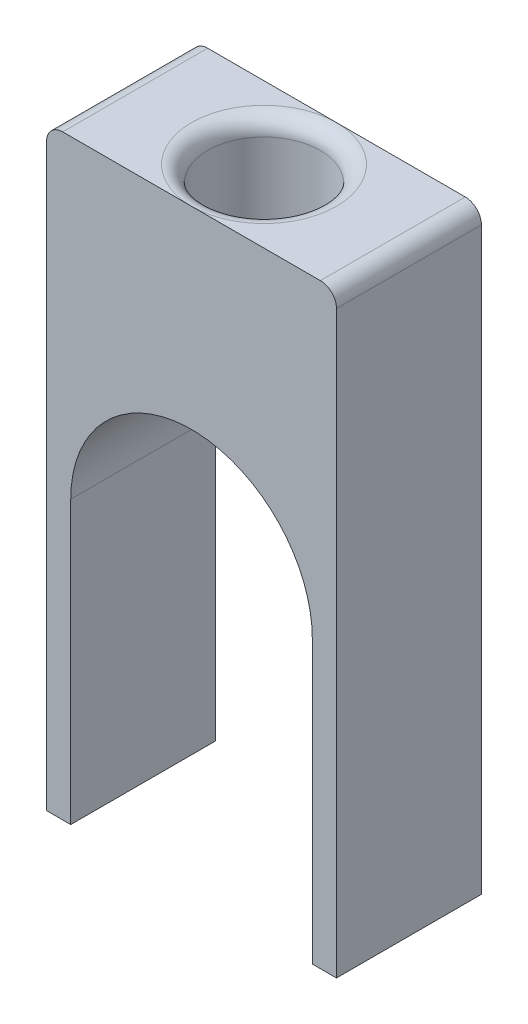
SolidWorks part; units mm, degrees
ref_plane "Front Plane" through (0, 0, 0) normal (0, 0, 1) x (1, 0, 0)
ref_plane "Top Plane" through (0, 0, 0) normal (0, 1, 0) x (1, 0, 0)
ref_plane "Right Plane" through (0, 0, 0) normal (1, 0, 0) x (0, 0, -1)
sketch "Sketch2" plane through (0, 0, 0) normal (0, 0, 1) x (1, 0, 0)
  line L0 (-21, 22) -> (-50021, 22) construction
  line L1 (-36, 74) -> (0, 74)
  line L2 (-36, 74) -> (-36, 0)
  line L3 (-36, 0) -> (0, 0)
  line L4 (0, 74) -> (0, 0)
  line L5 (-33.3871, 74) -> (-12.6168, 74)
  line L6 (-33, 35) -> (-33, 0)
  line L7 (-33, 0) -> (-3, 0)
  line L8 (-3, 35) -> (-3, 0)
  line L9 (-21, 28) -> (-50021, 28) construction
  arc A0 (-3, 35) -> (-33, 35) centre (-18, 35) ccw
  circle A1 centre (-18, 25) radius 3 construction
  circle A2 centre (-18, 35) radius 15 construction
  circle A3 centre (-18, 15) radius 15 construction
  point P11 (-18, 74)
  point P12 (-35, 35)
  dimension "D2" = 30
  dimension "D5" = 6
  dimension "D8" = 30
  dimension "D1" = 3
  dimension "D3" = 74
  dimension "D4" = 7
  dimension "D6" = 7
extrude "Boss-Extrude1" add sketch "Sketch2" along normal blind 18 contours L6 L1 L2 L3 | A0 L8 L1 L6 | L1 L8 L3 L4
sketch "Sketch3" plane through (0, 74, 0) normal (0, 1, 0) x (1, 0, 0)
  line L0 (-36, -18) -> (-36, 0) construction
  line L1 (-36, 0) -> (0, 0) construction
  circle A0 centre (-18, -9) radius 7
  point P2 (-36, -9)
  point P3 (-18, 0)
  dimension "D1" = 14
  dimension "D2" = 18
extrude "Cut-Extrude1" cut sketch "Sketch3" against normal up to surface (24 mm away)
fillet "Fillet1" radius 2 1 edges at (-18, 74, 16)
fillet "Fillet2" radius 2 2 edges at (-36, 74, 9) (0, 74, 9)
